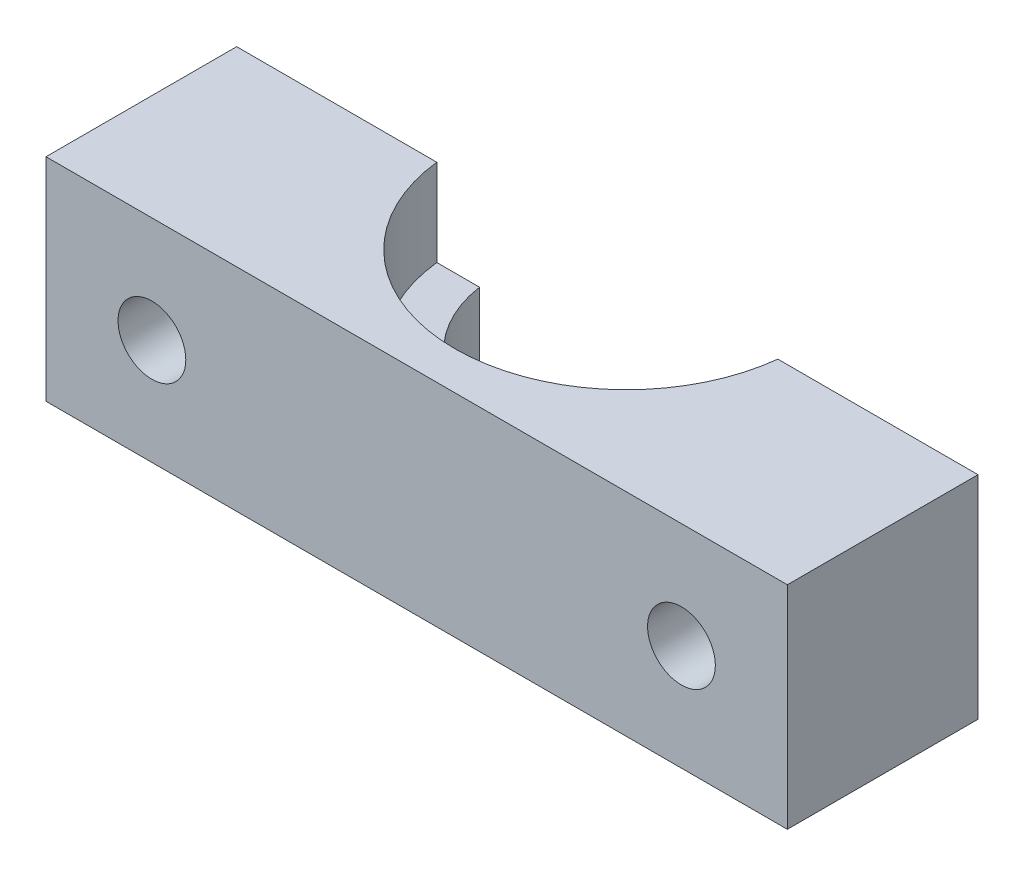
SolidWorks part; units mm, degrees
ref_plane "Front Plane" through (0, 0, 0) normal (0, 0, 1) x (1, 0, 0)
ref_plane "Top Plane" through (0, 0, 0) normal (0, 1, 0) x (1, 0, 0)
ref_plane "Right Plane" through (0, 0, 0) normal (1, 0, 0) x (0, 0, -1)
sketch "Sketch1" plane through (0, 0, 0) normal (0, 0, 1) x (1, 0, 0)
  line L1 (0, 0) -> (35, 0)
  line L2 (0, 0) -> (0, -27)
  line L3 (0, -27) -> (35, -27)
  line L4 (35, 0) -> (35, -27)
  circle A0 centre (10, -3.5) radius 1.5
  circle A1 centre (25, -3.5) radius 1.5
  circle A2 centre (10, -23.5) radius 1.5
  circle A3 centre (25, -23.5) radius 1.5
  dimension "D3" = 3
  dimension "D4" = 3
  dimension "D5" = 3
  dimension "D6" = 3
  dimension "D1" = 27
  dimension "D2" = 35
  dimension "D7" = 3.5
  dimension "D8" = 3.5
  dimension "D9" = 3.5
  dimension "D10" = 3.5
  dimension "D11" = 10
  dimension "D12" = 10
  dimension "D13" = 10
  dimension "D14" = 10
extrude "Boss-Extrude1" add sketch "Sketch1" along normal blind 25
sketch "Sketch3" plane through (0, 0, 0) normal (-1, 0, 0) x (0, 0, 1)
  line L1 (25, 0) -> (5, 0)
  line L2 (25, 0) -> (25, -10)
  line L3 (25, -10) -> (5, -10)
  line L4 (5, 0) -> (5, -10)
  line L5 (25, -27) -> (5, -27)
  line L6 (25, -27) -> (25, -20)
  line L7 (25, -20) -> (5, -20)
  line L8 (5, -27) -> (5, -20)
  dimension "D1" = 10
  dimension "D2" = 20
  dimension "D3" = 7
  dimension "D4" = 20
extrude "Cut-Extrude1" cut sketch "Sketch3" against normal through all
sketch "Sketch4" plane through (0, -10, 0) normal (0, 1, 0) x (1, 0, 0)
  line L6 (35, -5) -> (0, -5) construction
  line L7 (0, -5) -> (0, -25) construction
  circle A0 centre (17.4997, -15.1) radius 6.1
  point P6 (0, -15)
  dimension "D1" = 12.2
  dimension "D2" = 4
  dimension "D3" = 17.5
extrude "Cut-Extrude6" cut sketch "Sketch4" against normal through all
sketch "Sketch5" plane through (0, -10, 0) normal (0, 1, 0) x (1, 0, 0)
  circle A0 centre (17.4997, -15.1) radius 8.1
  dimension "D1" = 16.2
extrude "Cut-Extrude7" cut sketch "Sketch5" against normal blind 4.1
sketch "Sketch7" plane through (0, 0, 25) normal (0, 0, 1) x (1, 0, 0)
  line L0 (35, -10) -> (0, -10) construction
  line L1 (35, -10) -> (0, -10) construction
  line L2 (0, -10) -> (0, -20) construction
  line L3 (35, -20) -> (35, -10) construction
  circle A0 centre (5, -15) radius 1.6
  circle A1 centre (30, -15) radius 1.6
  dimension "D1" = 3.2
  dimension "D2" = 3.2
  dimension "D3" = 5
  dimension "D4" = 5
  dimension "D5" = 5
  dimension "D6" = 5
extrude "Cut-Extrude8" cut sketch "Sketch7" against normal through all
sketch "Sketch9" plane through (0, 0, 0) normal (0, 0, -1) x (-1, 0, 0)
  line L1 (-30, -11.95) -> (-32.6414, -13.475)
  line L2 (-32.6414, -13.475) -> (-32.6414, -16.525)
  line L3 (-32.6414, -16.525) -> (-30, -18.05)
  line L4 (-30, -18.05) -> (-27.3586, -16.525)
  line L5 (-27.3586, -16.525) -> (-27.3586, -13.475)
  line L6 (-27.3586, -13.475) -> (-30, -11.95)
  line L7 (-5, -11.95) -> (-7.6414, -13.475)
  line L8 (-7.6414, -13.475) -> (-7.6414, -16.525)
  line L9 (-7.6414, -16.525) -> (-5, -18.05)
  line L10 (-5, -18.05) -> (-2.3586, -16.525)
  line L11 (-2.3586, -16.525) -> (-2.3586, -13.475)
  line L12 (-2.3586, -13.475) -> (-5, -11.95)
  circle A0 centre (-30, -15) radius 2.6414 construction
  circle A1 centre (-5, -15) radius 2.6414 construction
  dimension "D1" = 6.1
  dimension "D2" = 6.1
extrude "Cut-Extrude9" cut sketch "Sketch9" against normal blind 10
sketch "Sketch10" plane through (0, 0, 0) normal (0, 0, -1) x (-1, 0, 0)
  line L1 (0, -27) -> (-35, -27)
  line L2 (0, -27) -> (0, 0)
  line L3 (0, 0) -> (-35, 0)
  line L4 (-35, -27) -> (-35, 0)
extrude "Cut-Extrude10" cut sketch "Sketch10" against normal blind 16
